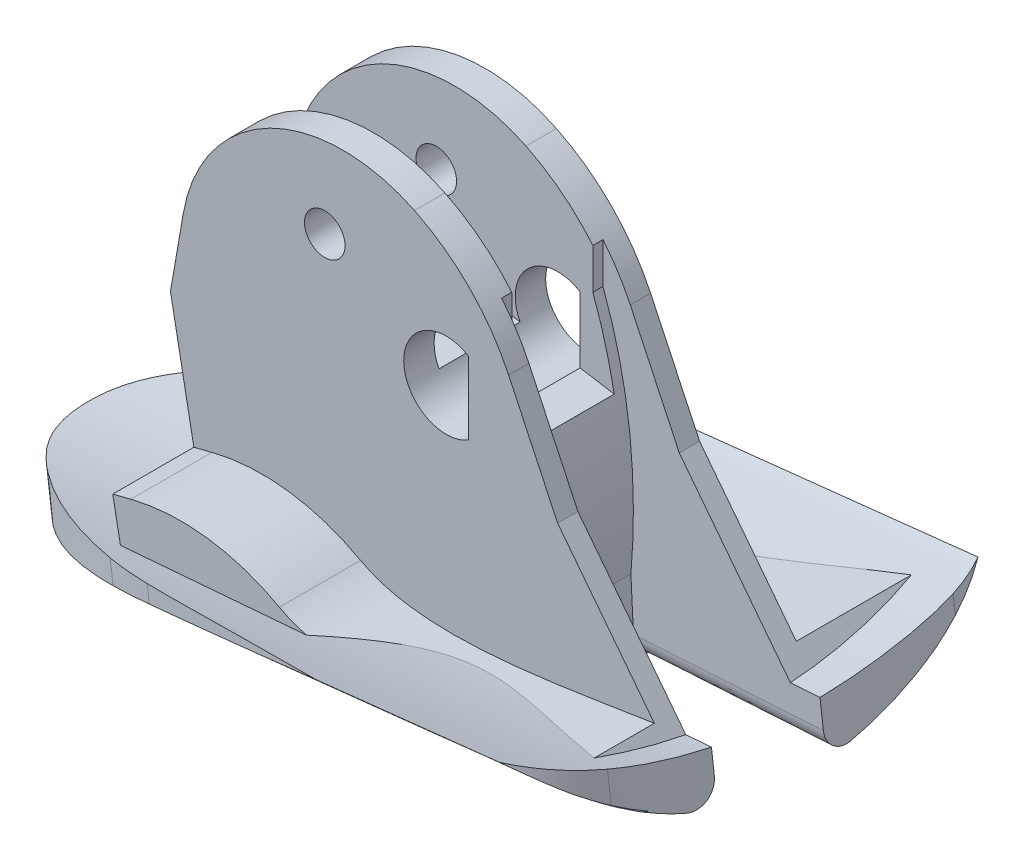
SolidWorks part; units mm, degrees
note: The reader was unsure of these and kept them because the rebuilt part matched: shared geometry of "Sketch11<2>".
ref_plane "Спереди" through (0, 0, 0) normal (0, 0, 1) x (1, 0, 0)
ref_plane "Сверху" through (0, 0, 0) normal (0, 1, 0) x (1, 0, 0)
ref_plane "Справа" through (0, 0, 0) normal (1, 0, 0) x (0, 0, -1)
sketch "Sketch5" plane through (0, 0, 0) normal (0, 0, 1) x (1, 0, 0)
  line L0 (1.7523, 0.4742) -> (37.3029, 86.8114) construction
  line L1 (-1.0106, -0.6044) -> (29.6618, 87.5839) construction
  line L2 (0, 0) -> (17.8901, 43.1295)
  line L3 (0, 0) -> (114.3643, 0) construction
  line L4 (23.8823, 39.6684) -> (24.5035, 51.2503)
  line B0 (17.4507, 115.16) -> (29.9551, 112.6983)
  spline B1 degree 3 poles (29.9551, 112.6983) (28.321, 116.0983) (27.9284, 121.1676) (30.1713, 134.4746) (29.8473, 132.0116) (30.6222, 139.9349) (27.0176, 140.9027) knots 0 0 0 0 0.297085 0.369784 0.687298 1 1 1 1
  spline B2 degree 2 poles (27.0176, 140.9027) (20.5603, 128.6427) (17.4507, 115.16) knots 0 0 0 1 1 1
  spline B3 degree 2 poles (27.0176, 140.9027) (26.5004, 134.6878) (22.2537, 130.5645) knots 0 0 0 1 1 1
  line B4 (17.1977, 114.3508) -> (29.842, 112.2111)
  line B5 (28.7001, 84.8969) -> (10.3668, 87.513)
  spline B6 degree 1 poles (17.1977, 114.3508) (10.3668, 87.513) knots 0 0 1 1
  spline B7 degree 2 poles (29.842, 112.2111) (22.5534, 98.8452) (28.7001, 84.8969) knots 0 0 0 1 1 1
  line B8 (10.1904, 87.4159) -> (28.2572, 84.4958)
  line B9 (32.8909, 45.7292) -> (10.0695, 42.8593)
  spline B10 degree 2 poles (10.1904, 87.4159) (10.0234, 65.1379) (10.0695, 42.8593) knots 0 0 0 1 1 1
  spline B11 degree 2 poles (28.2572, 84.4958) (20.6417, 64.1094) (32.8909, 45.7292) knots 0 0 0 1 1 1
  line B12 (10.2797, 36.8758) -> (3.9253, -13.9853)
  line B13 (3.9253, -13.9853) -> (33.9594, -31.0804)
  line B14 (33.9594, -31.0804) -> (45.9193, -27.7969)
  line B15 (45.9193, -27.7969) -> (58.2918, -13.9853)
  line B16 (58.2918, -13.9853) -> (69.0331, -4.9875)
  line B17 (69.0331, -4.9875) -> (82.514, 2.0236)
  line B18 (82.514, 2.0236) -> (89.2736, 3.8794)
  line B19 (89.2736, 3.8794) -> (92.4846, 9.5208)
  line B20 (92.4846, 9.5208) -> (96.8914, 17.263)
  line B21 (96.8914, 17.263) -> (101.4978, 21.1217)
  line B22 (101.4978, 21.1217) -> (103.9241, 23.1541)
  line B23 (104.261, 27.4157) -> (104.5375, 25.5318)
  line B24 (84.192, 21.2056) -> (87.7484, 22.7822)
  line B25 (87.7484, 22.7822) -> (92.912, 27.4956)
  line B26 (71.6086, 15.6268) -> (84.192, 21.2056)
  line B27 (92.912, 27.4956) -> (95.357, 29.7274)
  line B28 (95.357, 29.7274) -> (96.8049, 29.9399)
  line B29 (71.6086, 15.6268) -> (53.4239, 15.2713)
  line B30 (48.0904, 17.5622) -> (39.9394, 26.4919)
  line B31 (39.9394, 26.4919) -> (33.9594, 37.99)
  line B32 (33.9594, 37.99) -> (10.2797, 36.8758)
  line B33 (96.8049, 29.9399) -> (99.4078, 30.2175)
  line B34 (99.4078, 30.2175) -> (102.2786, 29.261)
  line B35 (102.2786, 29.261) -> (104.261, 27.4157)
  line B36 (104.5375, 25.5318) -> (103.9241, 23.1541)
  arc B37 (53.4239, 15.2713) -> (48.0904, 17.5622) centre (53.2864, 22.3051) cw
  spline B38 degree 3 poles (104.261, 27.4157) (103.5289, 27.0494) (99.8378, 26.2685) (94.8982, 17.2338) (98.6516, 18.7375) knots 0 0 0 0 0.441207 1 1 1 1
  line B39 (27.7375, 116.5129) -> (14.1959, 87.8955)
  line B40 (27.7375, 116.5129) -> (25.9485, 114.8372)
  line B41 (25.9485, 114.8372) -> (27.5763, 114.067)
  line B42 (27.7375, 116.5129) -> (27.5763, 114.067)
  line B43 (26.1527, 88.0864) -> (17.8901, 43.1295)
  line B44 (19.3622, 85.005) -> (23.8823, 39.6684)
  line B45 (19.3622, 85.005) -> (17.7584, 73.9508)
  line B46 (17.7584, 73.9508) -> (23.117, 74.485)
  line B47 (23.117, 74.485) -> (19.3622, 85.005)
  line B48 (26.1527, 88.0864) -> (23.7481, 82.7635)
  line B49 (23.7481, 82.7635) -> (25.1278, 82.5099)
  line B50 (25.1278, 82.5099) -> (26.5087, 82.2561)
  line B51 (26.5087, 82.2561) -> (26.1527, 88.0864)
  line B52 (26.1527, 88.0864) -> (19.3622, 85.005)
  line B53 (19.3622, 85.005) -> (22.3683, 87.7853)
  line B54 (22.3683, 87.7853) -> (22.9012, 86.6109)
  line B55 (22.9012, 86.6109) -> (23.4998, 85.2917)
  line B56 (23.4998, 85.2917) -> (19.3622, 85.005)
  dimension "D1" = 93.37
  dimension "D2" = 93.37
  dimension "D4" = 67.471
  dimension "D5" = 8.764
sketch_block_instance "Block1-1"
sketch_block "Block1"
sketch_block_instance "Block2-1"
sketch_block "Block2"
sketch_block_instance "Block3-1"
sketch_block "Block3"
sketch_block_instance "Block18-1"
sketch_block "Block18"
sketch_block_instance "Block44-1"
sketch_block "Block44"
sketch_block_instance "Block46-1"
sketch_block "Block46"
sketch_block_instance "Block47-1"
sketch_block "Block47"
sketch_block_instance "Block48-1"
sketch_block "Block48"
sketch_block_instance "Block50-1"
sketch_block "Block50"
sketch "Sketch10" plane through (0, 0, 0) normal (0, 0, 1) x (1, 0, 0)
  line L0 (24.801, 46.2069) -> (29.3738, 36.5215)
  line L3 (29.3738, 36.5215) -> (36.9938, 26.6828)
  line L4 (24.9823, 39.6684) -> (24.9823, 41.4572)
  line L5 (24.9823, 39.6684) -> (24.9823, 37.8795)
  line L21 (10.2797, 36.8758) -> (12.7888, 23.6588)
  line L22 (12.7888, 23.6588) -> (36.9938, 26.6828)
  line L23 (10.2797, 36.8758) -> (12.3218, 48.6569)
  line L24 (12.3218, 48.6569) -> (24.801, 46.2069)
  circle A0 centre (17.8901, 43.1295) radius 1
  arc A1 (24.9823, 41.4572) -> (24.9823, 37.8795) centre (23.8823, 39.6684) ccw
  dimension "D1" = 4.2
  dimension "D2" = 2
extrude "Boss-Extrude5" add sketch "Sketch10" along normal mid plane 15
sketch "Sketch11" plane through (0, 0, 7.5) normal (0, 0, 1) x (1, 0, 0)
  line L0 (17.8254, 32.4239) -> (9.1239, 30.2079)
  line L1 (37.7529, 30.846) -> (34.6935, 60.2717)
  line L2 (34.6935, 60.2717) -> (6.5943, 53.1599)
  line L3 (6.5943, 53.1599) -> (9.1239, 30.2079)
  line L4 (37.7529, 30.846) -> (30.6791, 30.1551) construction
  line L5 (30.6791, 30.1551) -> (19.269, 26.7342) construction
  line L6 (19.269, 26.7342) -> (17.8254, 32.4239) construction
  line L7 (12.3218, 48.6569) -> (10.2797, 36.8758) construction
  spline S1 degree 3 poles (37.7529, 30.846) (30.6791, 30.1551) (19.269, 26.7342) (17.8254, 32.4239) knots 0 0 0 0 1 1 1 1
extrude "Cut-Extrude1" cut sketch "Sketch11" against normal blind 4
fillet "Fillet1" radius 10 1 edges at (24.801, 46.2069, -2)
extrude "Cut-Extrude6" cut sketch "Sketch11<2>" against normal blind 10 from offset 11 offset against normal yes
sketch "Sketch11<2>" plane through (0, 0, 7.5) normal (0, 0, 1) x (1, 0, 0) same geometry as "Sketch11"
sketch "Sketch16" plane through (0, 0, 0) normal (0, 0, 1) x (1, 0, 0)
  line L1 (10.0743, 54.3608) -> (34.4186, 54.3608)
  line L2 (10.0743, 54.3608) -> (10.0743, 40.6451)
  line L3 (10.0743, 40.6451) -> (34.4186, 36.6644)
  line L4 (34.4186, 54.3608) -> (34.4186, 36.6644)
extrude "Cut-Extrude7" cut sketch "Sketch16" against normal mid plane 4
sketch "Sketch26" plane through (36.0406, 27.9136, 0) normal (0.7906, 0.6123, 0) x (0, 0, -1)
  line L15 (3.5, 10.8877) -> (-3.5, 10.8877)
  line L16 (-3.5, 10.8877) -> (-3.5, 3.0978)
  line L17 (-3.5, 3.0978) -> (-7.5, 3.0978)
  line L18 (-7.5, 3.0978) -> (-7.5, -1.5567)
  line L19 (-7.5, -1.5567) -> (7.5, -1.5567)
  line L20 (7.5, -1.5567) -> (7.5, 3.0978)
  line L21 (7.5, 3.0978) -> (3.5, 3.0978)
  line L22 (3.5, 3.0978) -> (3.5, 10.8877)
  line L27 (3.5, 10.8877) -> (-3.5, 10.8877)
  line L28 (-3.5, 10.8877) -> (-3.5, 3.0978)
  line L29 (-3.5, 3.0978) -> (-7.5, 3.0978)
  line L30 (-7.5, 3.0978) -> (-7.5, -1.5567)
  line L31 (-7.5, -1.5567) -> (7.5, -1.5567)
  line L32 (7.5, -1.5567) -> (7.5, 3.0978)
  line L33 (7.5, 3.0978) -> (3.5, 3.0978)
  line L34 (3.5, 3.0978) -> (3.5, 10.8877)
  dimension "D1" = 0
extrude "Boss-Extrude11" add sketch "Sketch26" along normal blind 9
sketch "Sketch28" plane through (0.9532, -1.2307, 0) normal (0.6123, -0.7906, 0) x (0.7906, 0.6123, 0)
  line L0 (38.2441, 4.6151) -> (38.2441, -4.6151) construction
  line L1 (54.5861, 0) -> (45.5861, 0) construction
  line L2 (54.5861, 7.5) -> (54.5861, -7.5) construction
  line L3 (45.5861, 7.5) -> (45.5861, -7.5) construction
  circle A0 centre (38.2441, 4.6151) radius 1
  circle A1 centre (38.2441, -4.6151) radius 1
  point P10 (38.2441, 0)
  dimension "D1" = 2
sketch "Sketch32" plane through (43.1561, 33.4245, 0) normal (0.7906, 0.6123, 0) x (0, 0, -1)
  line L16 (3.5, 10.8877) -> (-3.5, 10.8877)
  line L17 (-3.5, 10.8877) -> (-3.5, 3.0978)
  line L18 (-3.5, 3.0978) -> (-7.5, 3.0978)
  line L19 (-7.5, 3.0978) -> (-7.5, -1.5567)
  line L20 (-7.5, -1.5567) -> (7.5, -1.5567)
  line L21 (7.5, -1.5567) -> (7.5, 3.0978)
  line L22 (7.5, 3.0978) -> (3.5, 3.0978)
  line L23 (3.5, 3.0978) -> (3.5, 10.8877)
  line L28 (3.5, 10.8877) -> (-3.5, 10.8877)
  line L29 (-3.5, 10.8877) -> (-3.5, 3.0978)
  line L30 (-3.5, 3.0978) -> (-7.5, 3.0978)
  line L31 (-7.5, 3.0978) -> (-7.5, -1.5567)
  line L32 (-7.5, -1.5567) -> (7.5, -1.5567)
  line L33 (7.5, -1.5567) -> (7.5, 3.0978)
  line L34 (7.5, 3.0978) -> (3.5, 3.0978)
  line L35 (3.5, 3.0978) -> (3.5, 10.8877)
  dimension "D1" = 0
extrude "Cut-Extrude9" cut sketch "Sketch32" against normal blind 9
fillet "Fillet2" radius 8 2 edges at (12.3218, 48.6569, 2.75) (12.3218, 48.6569, -2.75)
fillet "Fillet3" radius 10 2 edges at (17.8254, 32.4239, 5.5) (17.8254, 32.4239, -5.5)
sketch "Sketch33" plane through (0, 0, -7.5) normal (0, 0, -1) x (-1, 0, 0)
  line L8 (-11.4338, 30.7962) -> (-12.3264, 31.0235)
  line L9 (-34.1438, 30.3627) -> (-36.9938, 26.6828)
  line L10 (-36.9938, 26.6828) -> (-12.7888, 23.6588)
  line L15 (-12.7888, 23.6588) -> (-11.4338, 30.7962)
  line L16 (-11.4338, 30.7962) -> (-12.3264, 31.0235)
  line L17 (-34.1438, 30.3627) -> (-36.9938, 26.6828)
  line L18 (-36.9938, 26.6828) -> (-12.7888, 23.6588)
  line L23 (-12.7888, 23.6588) -> (-11.4338, 30.7962)
  arc A1 (-12.3264, 31.0235) -> (-19.6523, 30.0735) centre (-14.7943, 21.3328) ccw
  arc A2 (-12.3264, 31.0235) -> (-19.6523, 30.0735) centre (-14.7943, 21.3328) ccw
  spline S1 degree 3 poles (-2248.4331, 2036.9035) (2398.5946, -1976.7775) (-2489.4145, 2007.6298) (2270.2063, -1890.107) knots -4.784793 -4.784793 -4.784793 -4.784793 6.243162 6.243162 6.243162 6.243162 only from (-19.6523, 30.0735) to (-34.1438, 30.3627)
  spline S2 degree 3 poles (-19.6523, 30.0735) (-22.7361, 28.3596) (-28.8813, 29.5444) (-34.1438, 30.3627) knots 0.191604 0.191604 0.191604 0.191604 0.842502 0.842502 0.842502 0.842502
  dimension "D1" = 0
extrude "Boss-Extrude15" add sketch "Sketch33" along normal blind 2
ref_plane "Plane1" through (36.5972, 26.9065, -1.1603) normal (-0.9966, -0.0705, 0.0433) x (0.0432, 0.0031, 0.9991)
sketch "Sketch34" plane through (36.5972, 26.9065, -1.1603) normal (-0.9966, -0.0705, 0.0433) x (0.0432, 0.0031, 0.9991)
  line L0 (10.9628, 4.6222) -> (3.477, -2.4087) construction
  line L2 (3.477, -2.4087) -> (-3.5213, -0.2511) construction
  line L4 (-3.5213, -0.2511) -> (-6.924, 1.4367) construction
  line L5 (-6.924, 1.4367) -> (-9.806, 4.1457) construction
  line L6 (8.6686, -0.2511) -> (-8.3155, -0.2511) construction
  line L7 (10.9628, 4.6222) -> (5.1029, 2.7181) construction
  line L8 (5.1029, 2.7181) -> (1.0957, 2.098) construction
  line L9 (1.0957, 2.098) -> (-5.2968, 2.5273) construction
  line L10 (-5.2968, 2.5273) -> (-9.806, 4.1457) construction
  spline S0 degree 4 poles (10.9628, 4.6222) (3.477, -2.4087) (-3.5213, -0.2511) (-6.924, 1.4367) (-9.806, 4.1457) knots 0 0 0 0 0 1 1 1 1 1
  spline S1 degree 4 poles (10.9628, 4.6222) (5.1029, 2.7181) (1.0957, 2.098) (-5.2968, 2.5273) (-9.806, 4.1457) knots 0 0 0 0 0 1 1 1 1 1
extrude "Boss-Extrude16" add sketch "Sketch34" along normal blind 50 and the other way blind 10
sketch "Sketch35" plane through (-2.7138, 21.7221, 0) normal (0.124, -0.9923, 0) x (0.9923, 0.124, 0)
  line L2 (39.6124, -9.2736) -> (39.614, -9.2589)
  circle A0 centre (27.3927, -0.6279) radius 55.4026
  spline S32 degree 3 poles (24.9565, -10.7059) (25.5212, -10.8521) (26.0851, -10.9988) (27.2128, -11.2896) (27.7763, -11.4341) (28.3423, -11.5719) knots 0 0 0 0 0.5 0.5 1 1 1 1
  spline S33 degree 3 poles (19.0873, -9.1591) (20.0581, -9.4433) (21.0399, -9.6954) (22.9999, -10.202) (23.9795, -10.4528) (24.9565, -10.7059) knots 0 0 0 0 0.5 0.5 1 1 1 1
  spline S34 degree 3 poles (15.2528, -7.7133) (15.8688, -8.0055) (16.4922, -8.2786) (17.7718, -8.7565) (18.4259, -8.9655) (19.0873, -9.1591) knots 0 0 0 0 0.5 0.5 1 1 1 1
  spline S35 degree 3 poles (8.1536, -3.0322) (8.4043, -3.2912) (8.6672, -3.5343) (9.2066, -4.0025) (9.4833, -4.227) (10.3296, -4.879) (10.9159, -5.2857) (12.1173, -6.0499) (12.7309, -6.4082) (13.9786, -7.0877) (14.6116, -7.4091) (15.2528, -7.7133) knots 0 0 0 0 0.125 0.125 0.25 0.25 0.5 0.5 0.75 0.75 1 1 1 1
  spline S36 degree 3 poles (6.8672, -1.0785) (6.9335, -1.2667) (7.0135, -1.4502) (7.1946, -1.8009) (7.2957, -1.9686) (7.6253, -2.4524) (7.8798, -2.7495) (8.1536, -3.0322) knots 0 0 0 0 0.25 0.25 0.5 0.5 1 1 1 1
  spline S37 degree 3 poles (7.0947, 2.5911) (6.9606, 2.3051) (6.8532, 2.0075) (6.6972, 1.4025) (6.6472, 1.0933) (6.6049, 0.4613) (6.614, 0.1448) (6.692, -0.4743) (6.7617, -0.7791) (6.8672, -1.0785) knots 0 0 0 0 0.25 0.25 0.5 0.5 0.75 0.75 1 1 1 1
  spline S38 degree 3 poles (8.5033, 4.4734) (8.2174, 4.1997) (7.9498, 3.9116) (7.4739, 3.2892) (7.2653, 2.9551) (7.0947, 2.5911) knots 0 0 0 0 0.5 0.5 1 1 1 1
  spline S39 degree 3 poles (15.981, 8.6546) (15.2904, 8.4399) (14.6155, 8.1883) (13.2929, 7.6281) (12.645, 7.3153) (11.3861, 6.6266) (10.7736, 6.2482) (9.89, 5.6274) (9.6016, 5.4119) (9.0397, 4.9603) (8.7657, 4.7246) (8.5033, 4.4734) knots 0 0 0 0 0.25 0.25 0.5 0.5 0.75 0.75 0.875 0.875 1 1 1 1
  spline S40 degree 3 poles (18.362, 9.1871) (17.9562, 9.1266) (17.5535, 9.0566) (16.7592, 8.8815) (16.3681, 8.7749) (15.981, 8.6546) knots 0 0 0 0 0.5 0.5 1 1 1 1
  spline S41 degree 3 poles (29.3353, 10.4123) (28.4207, 10.3194) (27.5084, 10.2133) (25.6823, 10.0027) (24.7686, 9.8978) (22.9384, 9.699) (22.0218, 9.6059) (20.647, 9.4639) (20.1887, 9.4158) (19.2736, 9.3113) (18.8167, 9.2551) (18.362, 9.1871) knots 0 0 0 0 0.25 0.25 0.5 0.5 0.75 0.75 0.875 0.875 1 1 1 1
  spline S42 degree 3 poles (38.6158, 6.7752) (38.4879, 7.1918) (38.3336, 7.5867) (37.9581, 8.3332) (37.7427, 8.6893) (37.3485, 9.165) (37.2045, 9.3143) (36.8928, 9.5962) (36.7245, 9.7296) (36.3583, 9.974) (36.1635, 10.0827) (35.7443, 10.269) (35.5168, 10.3471) (35.0463, 10.4694) (34.8043, 10.5144) (34.311, 10.582) (34.0586, 10.6045) (33.3074, 10.6477) (32.8089, 10.6463) (31.8139, 10.6152) (31.3175, 10.5849) (30.3258, 10.5087) (29.8304, 10.4626) (29.3353, 10.4123) knots 0 0 0 0 0.125 0.125 0.25 0.25 0.3125 0.3125 0.375 0.375 0.4375 0.4375 0.5 0.5 0.5625 0.5625 0.625 0.625 0.75 0.75 0.875 0.875 1 1 1 1
  spline S43 degree 3 poles (39.614, -9.2589) (39.6788, -8.6788) (39.7035, -8.0722) (39.7298, -6.8066) (39.7311, -6.1432) (39.7281, -4.7965) (39.7222, -4.1108) (39.7072, -3.0634) (39.701, -2.7112) (39.6835, -2.0003) (39.6718, -1.6404) (39.6244, -0.5691) (39.5786, 0.1385) (39.4668, 1.5416) (39.4008, 2.239) (39.2432, 3.6136) (39.1532, 4.2784) (38.93, 5.5624) (38.7979, 6.1818) (38.6158, 6.7752) knots 0 0 0 0 0.125 0.125 0.25 0.25 0.375 0.375 0.4375 0.4375 0.5 0.5 0.625 0.625 0.75 0.75 0.875 0.875 1 1 1 1
  spline S44 degree 3 poles (38.1236, -12.3487) (38.2624, -12.2667) (38.3838, -12.1721) (38.6007, -11.9688) (38.6957, -11.8604) (38.9537, -11.5192) (39.0907, -11.2681) (39.3113, -10.7408) (39.3963, -10.4645) (39.4986, -10.0321) (39.5255, -9.8845) (39.5737, -9.5834) (39.5946, -9.43) (39.6124, -9.2736) knots 0 0 0 0 0.125 0.125 0.25 0.25 0.5 0.5 0.75 0.75 0.875 0.875 1 1 1 1
  spline S45 degree 3 poles (37.8947, -12.4638) (37.9761, -12.4297) (38.0519, -12.391) (38.1236, -12.3487) knots 0 0 0 0 1 1 1 1
  spline S46 degree 3 poles (34.5417, -12.5645) (34.828, -12.587) (35.1142, -12.6076) (35.6868, -12.6412) (35.9731, -12.6544) (36.5456, -12.6643) (36.8315, -12.6617) (37.2498, -12.6244) (37.389, -12.6058) (37.6533, -12.5499) (37.7782, -12.5125) (37.8947, -12.4638) knots 0 0 0 0 0.25 0.25 0.5 0.5 0.75 0.75 0.875 0.875 1 1 1 1
  spline S47 degree 3 poles (28.3423, -11.5719) (29.3519, -11.8178) (30.3705, -12.041) (32.442, -12.3728) (33.4913, -12.4819) (34.5417, -12.5645) knots 0 0 0 0 0.5 0.5 1 1 1 1
extrude "Cut-Extrude10" cut sketch "Sketch35" against normal blind 30 and the other way blind 72
sketch "Sketch36" plane through (36.5972, 26.9065, -1.1603) normal (-0.9966, -0.0705, 0.0433) x (0.0432, 0.0031, 0.9991)
  line L1 (-11.6294, 6.1274) -> (-6.4307, -1.0001) construction
  line L2 (-6.4307, -1.0001) -> (3.088, -1.7462) construction
  line L3 (3.088, -1.7462) -> (7.2256, 0.8941) construction
  line L5 (7.2256, 0.8941) -> (11.8416, 5.5345) construction
  line L6 (-11.6294, 6.1274) -> (-10.8368, -5.0459)
  line L7 (-10.8368, -5.0459) -> (4.6769, -6.7725)
  line L8 (4.6769, -6.7725) -> (13.0264, -2.4689)
  line L9 (13.0264, -2.4689) -> (11.8416, 5.5345)
  spline S0 degree 4 poles (-11.6294, 6.1274) (-6.4307, -1.0001) (3.088, -1.7462) (7.2256, 0.8941) (11.8416, 5.5345) knots 0 0 0 0 0 1 1 1 1 1
extrude "Cut-Extrude11" cut sketch "Sketch36" along normal blind 35 and the other way blind 10
sketch "Sketch37" plane through (0, 0, 0) normal (0, 1, 0) x (1, 0, 0)
  circle A0 centre (31.576, 4.5788) radius 1.0332
  circle A1 centre (31.576, -4.6483) radius 1.025
sketch "Sketch38" plane through (0, 0, 0) normal (0, 0, 1) x (1, 0, 0)
  line L0 (25.6108, 47.7844) -> (25.6108, 41.7534)
  line L1 (26.9876, 30.1593) -> (27.4181, 21.425)
  line L2 (27.4181, 21.425) -> (39.9211, 21.425)
  line L3 (39.9211, 21.425) -> (37.073, 47.7844)
  line L4 (37.073, 47.7844) -> (25.6108, 47.7844)
  line L6 (25.6108, 41.7534) -> (27.5342, 36.6066) construction
  line L7 (27.5342, 36.6066) -> (26.9876, 30.1593) construction
  spline S0 degree 2 poles (25.6108, 41.7534) (27.5342, 36.6066) (26.9876, 30.1593) knots 0 0 0 1 1 1
extrude "Cut-Extrude13" cut sketch "Sketch38" against normal mid plane 5
fillet "Fillet4" radius 1 2 edges
